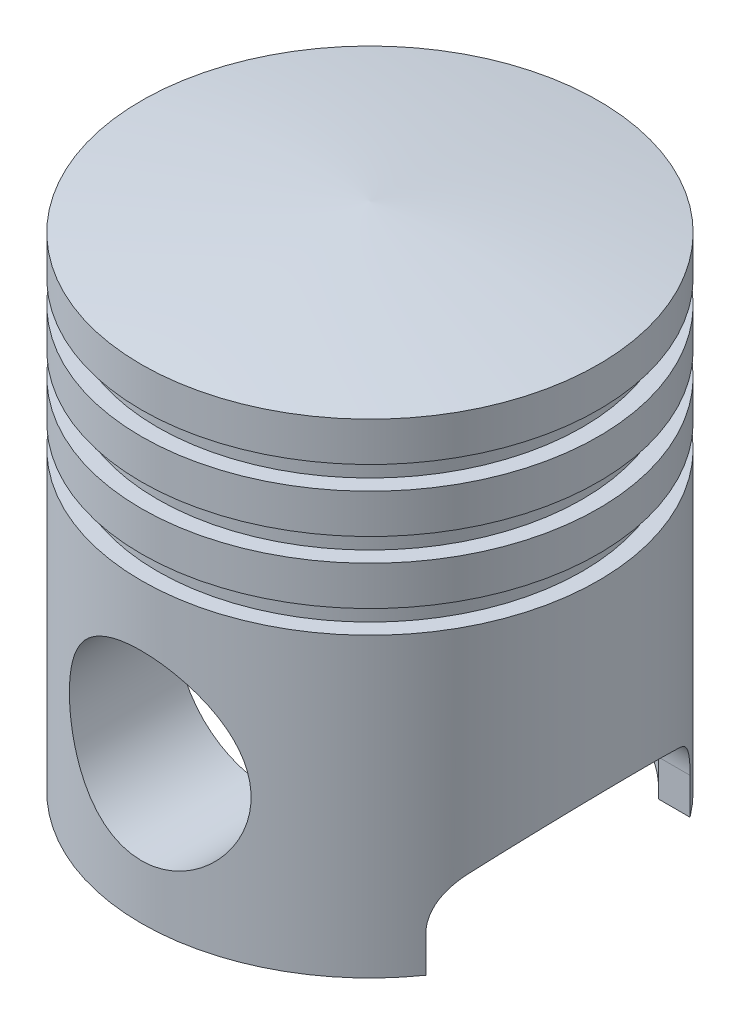
SolidWorks part; units mm, degrees
ref_plane "Front Plane" through (0, 0, 0) normal (0, 0, 1) x (1, 0, 0)
ref_plane "Top Plane" through (0, 0, 0) normal (0, 1, 0) x (1, 0, 0)
ref_plane "Right Plane" through (0, 0, 0) normal (1, 0, 0) x (0, 0, -1)
sketch "Sketch1" plane through (0, 0, 0) normal (0, 0, 1) x (1, 0, 0)
  line L0 (0, 65.6398) -> (0, -68.2098) construction
  line L1 (42.5, 42.5) -> (42.5, 35.2)
  line L2 (42.5, 35.2) -> (39.5, 35.2)
  line L3 (39.5, 35.2) -> (39.5, 30.9)
  line L4 (39.5, 30.9) -> (42.5, 30.9)
  line L5 (42.5, 30.9) -> (42.5, 23.6)
  line L6 (42.5, 23.6) -> (39.5, 23.6)
  line L7 (39.5, 23.6) -> (39.5, 19.3)
  line L8 (39.5, 19.3) -> (42.5, 19.3)
  line L9 (42.5, 19.3) -> (42.5, 12)
  line L10 (42.5, 12) -> (39.5, 12)
  line L11 (39.5, 12) -> (39.5, 7.7)
  line L12 (39.5, 7.7) -> (42.5, 7.7)
  line L13 (42.5, 7.7) -> (42.5, -47.5)
  line L14 (38, 38.2) -> (38, 2)
  line L15 (38, 38.2) -> (0, 38.2)
  line L16 (0, 38.2) -> (0, 47.5)
  line L17 (38, 2) -> (19, 2)
  line L18 (19, 2) -> (19, -43.5)
  line L19 (19, -43.5) -> (38, -43.5)
  line L20 (38, -43.5) -> (38, -47.5)
  line L21 (38, -47.5) -> (42.5, -47.5)
  arc A0 (0, 47.5) -> (42.5, 42.5) centre (-34.5522, -429.3188) cw
  point P13 (39.5, 33.05)
  dimension "D8" = 38
  dimension "D14" = 478.0691
  dimension "D1" = 95
  dimension "D2" = 47.5
  dimension "D3" = 42.5
  dimension "D4" = 7.3
  dimension "D5" = 4.3
  dimension "D6" = 39.5
  dimension "D7" = 5
  dimension "D9" = 19
  dimension "D10" = 4.3
  dimension "D11" = 49.5
  dimension "D12" = 38
  dimension "D13" = 4
revolve "Revolve1" add sketch "Sketch1" angle 360 about L0
sketch "Sketch2" plane through (0, 0, 0) normal (0, 0, 1) x (1, 0, 0)
  line L0 (0, -53.8451) -> (0, 55.0483) construction
  circle A0 centre (0, -20.5) radius 16.9
  circle A1 centre (0, -20.5) radius 22.5
  dimension "D2" = 33.8
  dimension "D1" = 45
sketch "Sketch4" plane through (0, 0, 0) normal (1, 0, 0) x (0, 0, -1)
  line L0 (-24.3984, -47.5) -> (25.6016, -47.5)
  line L1 (25.6016, -47.5) -> (25.6016, -40.7442)
  line L2 (-24.3984, -47.5) -> (-24.3984, -40.7442)
  line L3 (-42.5, -47.5) -> (42.5, -47.5) construction
  arc A0 (20.6016, -32.084) -> (-19.3984, -32.084) centre (0.6016, -66.725) ccw
  arc A1 (-24.3984, -40.7442) -> (-19.3984, -32.084) centre (-14.3984, -40.7442) cw
  arc A2 (25.6016, -40.7442) -> (20.6016, -32.084) centre (15.6016, -40.7442) ccw
  point P3 (0.6016, -47.5)
  dimension "D2" = 10
  dimension "D3" = 10
  dimension "D1" = 50
extrude "Cut-Extrude2" cut sketch "Sketch4" against normal mid plane 130
sketch "Sketch5" plane through (0, -47.5, 0) normal (0, -1, 0) x (1, 0, 0)
  circle A0 centre (0, 0) radius 38
extrude "Cut-Extrude3" cut sketch "Sketch5" against normal up to surface (85.7 mm away) up to face at (0, 38.2, 38)
extrude "Boss-Extrude2" add sketch "Sketch2" along normal up to next from offset 19 contours A0 | A1
mirror "Mirror1" about plane through (0, 0, 0) normal (0, 0, 1) of "Boss-Extrude2"
extrude "Cut-Extrude4" cut sketch "Sketch2<4>" against normal mid plane 130 contours A0
sketch "Sketch2<4>" plane through (0, 0, 0) normal (0, 0, 1) x (1, 0, 0) same geometry as "Sketch2"
